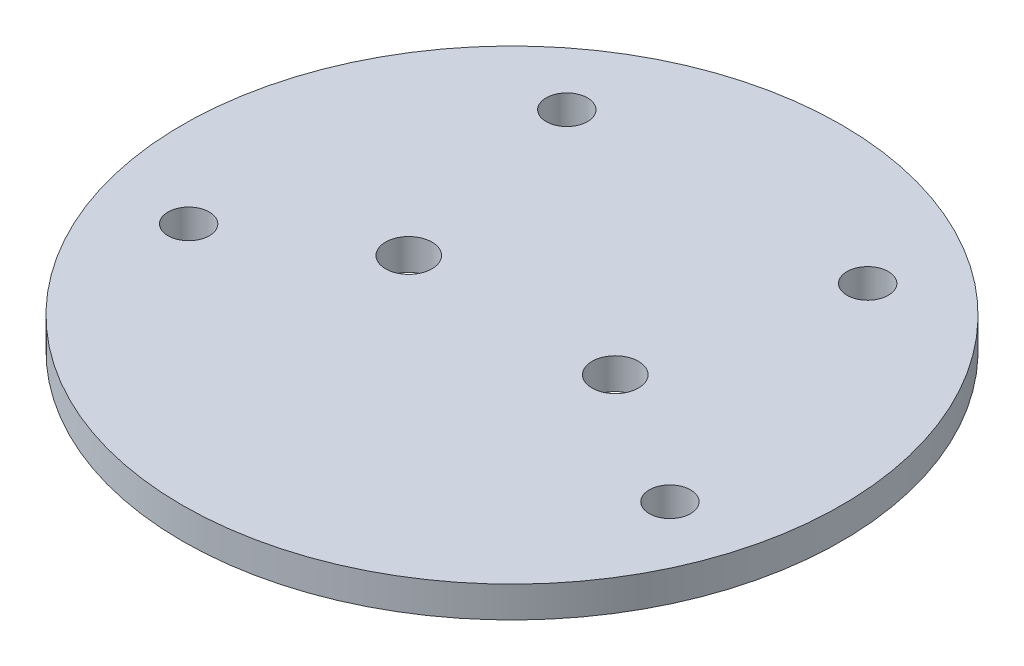
SolidWorks part; units mm, degrees
material "5052-H32"
ref_plane "Front Plane" through (0, 0, 0) normal (0, 0, 1) x (1, 0, 0)
ref_plane "Top Plane" through (0, 0, 0) normal (0, 1, 0) x (1, 0, 0)
ref_plane "Right Plane" through (0, 0, 0) normal (1, 0, 0) x (0, 0, -1)
sketch "Sketch1" plane through (0, 0, 0) normal (0, 1, 0) x (1, 0, 0)
  line L0 (0, 0) -> (-23.1297, 31.5565) construction
  line L1 (0, 0) -> (-41.7254, 0) construction
  line L2 (-37.0005, -12.7186) -> (0, 0) construction
  line L3 (0, -31.6103) -> (0, 47.1695) construction
  circle A0 centre (0, 0) radius 50.673
  circle A3 centre (-15.875, 0) radius 3.5687
  circle A4 centre (15.875, 0) radius 3.5687
  circle A5 centre (-37.0005, -12.7186) radius 3.175
  circle A8 centre (-23.1297, 31.5565) radius 3.175
  circle A9 centre (23.1297, 31.5565) radius 3.175
  circle A10 centre (37.0005, -12.7186) radius 3.175
  dimension "D1" = 101.346
  dimension "D2" = 6.35
  dimension "D3" = 6.35
  dimension "D5" = 15.875
  dimension "D6" = 15.875
  dimension "D4" = 39.1254
  dimension "D7" = 53.76
  dimension "D8" = 39.1254
  dimension "D9" = 18.97
extrude "Boss-Extrude1" add sketch "Sketch1" along normal blind 4.7752
equation "\"allrockets_tube_ID\"= 3.85in"
equation "\"allrockets_tube_OD\"= 4.024in"
equation "\"hole\"= 6.35mm"
equation "\"back_plate_width\"= 28mm"
equation "\"card_spacing\"= 20mm"
equation "\"card_number\"= 6"
equation "\"ToDi\"= 0.05mm"
equation "\"card_diameter\"= 85.86mm"
equation "\"overlap\"= 6.6mm"
equation "\"card_length\"= 68mm"
equation "\"rack_hole_tol\"= 0.60mm"
equation "\"rack_front_width\"= 11.63mm"
equation "\"hole_b_d\"= 39.12541885mm"
equation "\"hole_b_a\"= 18.9721389deg"
equation "\"hole_u_d\"= 39.12541885mm"
equation "\"hole_u_a\"= 53.76090642deg"
equation "\"card_h\"= 61.73mm"
equation "\"sphinx_av\"= 50.292mm"
equation "\"tb_spacing\"= 40mm"
equation "\"D2@Sketch1\"=\"hole\""
equation "\"D4@Sketch1\"=\"hole_u_d\""
equation "\"D7@Sketch1\"=\"hole_u_a\""
equation "\"D8@Sketch1\"=\"hole_b_d\""
equation "\"D9@Sketch1\"=\"hole_b_a\""
